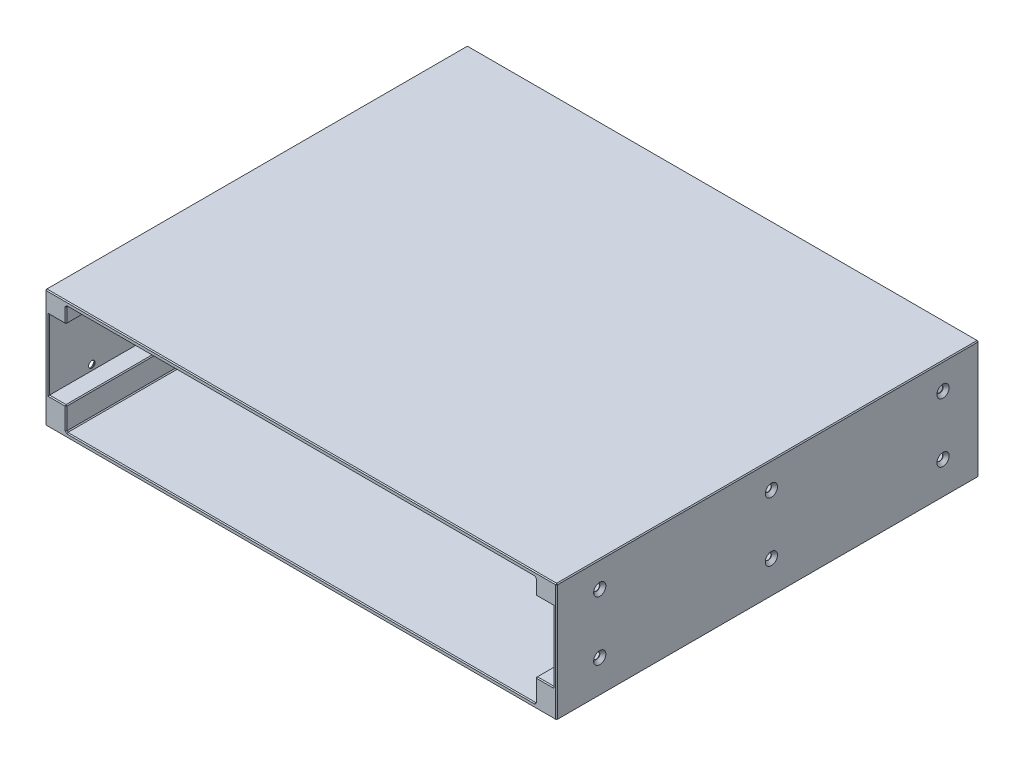
SolidWorks part; units mm, degrees
ref_plane "Front" through (0, 0, 0) normal (0, 0, 1) x (1, 0, 0)
ref_plane "Top" through (0, 0, 0) normal (0, 1, 0) x (1, 0, 0)
ref_plane "Right" through (0, 0, 0) normal (1, 0, 0) x (0, 0, -1)
sketch "Sketch1" plane through (0, 0, 0) normal (0, 0, 1) x (1, 0, 0)
  line L1 (-138, -30) -> (138, -30)
  line L2 (-138, -30) -> (-138, 30)
  line L3 (-138, 30) -> (138, 30)
  line L4 (138, -30) -> (138, 30)
  line L5 (-138, -30) -> (138, 30) construction
  line L6 (-138, 30) -> (138, -30) construction
  point P0 (0, 0)
  dimension "D1" = 276
  dimension "D2" = 60
extrude "Walls" add sketch "Sketch1" along normal blind 230 thin thin type one direction wall 2.5
sketch "Sketch2" plane through (0, 0, 0) normal (0, 0, 1) x (1, 0, 0)
  line L12 (140.5, -32.5) -> (140.5, 32.5)
  line L13 (140.5, 32.5) -> (-140.5, 32.5)
  line L14 (-140.5, 32.5) -> (-140.5, -32.5)
  line L15 (-140.5, -32.5) -> (140.5, -32.5)
  line L16 (140.5, -32.5) -> (140.5, 32.5)
  line L17 (140.5, 32.5) -> (-140.5, 32.5)
  line L18 (-140.5, 32.5) -> (-140.5, -32.5)
  line L19 (-140.5, -32.5) -> (140.5, -32.5)
  dimension "D1" = 0
extrude "Back Plate" add sketch "Sketch2" against normal blind 2
sketch "Sketch7" plane through (138.5, 0, 0) normal (1, 0, 0) x (0, 0, -1)
  line L0 (0, -30) -> (0, 30) construction
  line L1 (0, -17.25) -> (-230, -17.25)
  line L2 (0, -17.25) -> (0, 21.25)
  line L3 (0, 21.25) -> (-230, 21.25)
  line L4 (-230, -17.25) -> (-230, 21.25)
  line L5 (-230, -32.5) -> (-230, 32.5) construction
extrude "Drawer Slide Pocket" cut sketch "Sketch7" against normal up to next
sketch "Sketch8" plane through (138, 0, 0) normal (-1, 0, 0) x (0, 0, 1)
  line L0 (230, 32.5) -> (230, -32.5) construction
  line L1 (0, -30) -> (230, -30)
  line L2 (0, -30) -> (0, -17.25)
  line L3 (0, -17.25) -> (230, -17.25)
  line L4 (230, -30) -> (230, -17.25)
  line L6 (0, 30) -> (230, 30)
  line L7 (0, 30) -> (0, 21.25)
  line L8 (0, 21.25) -> (230, 21.25)
  line L9 (230, 30) -> (230, 21.25)
extrude "Drawer Slide Brackets" add sketch "Sketch8" along normal blind 9
sketch "Sketch9" plane through (140.5, 0, 0) normal (1, 0, 0) x (0, 0, -1)
  point P0 (-206.2857, -14.25)
  point P1 (-206.2857, 18.25)
  point P3 (-112, -14.25)
  point P5 (-112, 18.25)
  point P7 (-17.7143, -14.25)
  point P9 (-17.7143, 18.25)
hole_wizard "CSK for M3 SFHCS1" positions "Sketch9" profile "Sketch10" countersink size "M3" standard "ANSI Metric" end condition up to next
sketch "Sketch10" plane through (140.5, -14.25, 206.2857) normal (0, 1, 0) x (0, 0, -1)
  line L0 (0, 0) -> (0, 2)
  line L1 (0, 2) -> (1.8, 2)
  line L2 (1.7, 1.9) -> (1.7, 1.66)
  line L3 (1.7, 1.66) -> (3.36, 0)
  line L5 (3.36, 0) -> (0, 0)
  line L6 (-1.7, 1.66) -> (-3.36, 0) construction
  line L7 (1.8, 2) -> (1.7, 1.9)
  line L8 (-1.8, 2) -> (-1.7, 1.9) construction
  line L11 (0, -6.35) -> (0, 107.95) construction
  dimension "Thru Hole Dia." = 3.4
  dimension "Thru Hole Depth" = 2
  dimension "Near C'Sink Dia." = 6.72
  dimension "Near C'Sink Angle" = 90
  dimension "Far C'Sink Dia." = 3.6
  dimension "Far C'Sink Angle" = 90
mirror "Drawer Slide Pocket mirror" about plane through (0, 0, 0) normal (1, 0, 0) of "CSK for M3 SFHCS1", "Drawer Slide Pocket", "Drawer Slide Brackets"
sketch "Sketch3" plane through (0, -32.5, 0) normal (0, 1, 0) x (1, 0, 0)
  line L0 (0, 2) -> (0, -114) construction
  line L1 (-114.5192, -23.9808) -> (114.5192, -23.9808) construction
  line L2 (-114.5192, -23.9808) -> (-114.5192, -204.0192) construction
  line L3 (-114.5192, -204.0192) -> (114.5192, -204.0192) construction
  line L4 (114.5192, -23.9808) -> (114.5192, -204.0192) construction
  line L5 (-114.5192, -23.9808) -> (114.5192, -204.0192) construction
  line L6 (-114.5192, -204.0192) -> (114.5192, -23.9808) construction
  line L8 (0, -114) -> (0, -230) construction
  line L10 (-140.5, -23.9808) -> (-114.5192, -23.9808) construction
  line L11 (140.5, 2) -> (-140.5, 2) construction
  line L12 (-114.5192, -23.9808) -> (-114.5192, 2) construction
  line L13 (-57.2596, -23.9808) -> (-57.2596, -15.3205) construction
  line L14 (-114.5192, -32.641) -> (-107.0192, -28.3109)
  line L15 (-107.0192, -28.3109) -> (-107.0192, -19.6506)
  line L16 (-107.0192, -19.6506) -> (-114.5192, -15.3205)
  line L17 (-114.5192, -15.3205) -> (-122.0192, -19.6506)
  line L18 (-122.0192, -19.6506) -> (-122.0192, -28.3109)
  line L19 (-122.0192, -28.3109) -> (-114.5192, -32.641)
  line L20 (-57.2596, -15.3205) -> (-57.2596, -6.6603) construction
  line L21 (0, -114) -> (114.5192, -114) construction
  line L22 (122.0192, -28.3109) -> (114.5192, -32.641)
  line L23 (122.0192, -19.6506) -> (122.0192, -28.3109)
  line L24 (114.5192, -15.3205) -> (122.0192, -19.6506)
  line L25 (107.0192, -19.6506) -> (114.5192, -15.3205)
  line L26 (107.0192, -28.3109) -> (107.0192, -19.6506)
  line L27 (114.5192, -32.641) -> (107.0192, -28.3109)
  line L28 (122.0192, -208.3494) -> (122.0192, -199.6891)
  line L29 (114.5192, -212.6795) -> (122.0192, -208.3494)
  line L30 (107.0192, -208.3494) -> (114.5192, -212.6795)
  line L31 (107.0192, -199.6891) -> (107.0192, -208.3494)
  line L32 (114.5192, -195.359) -> (107.0192, -199.6891)
  line L33 (122.0192, -199.6891) -> (114.5192, -195.359)
  line L34 (-122.0192, -199.6891) -> (-114.5192, -195.359)
  line L35 (-122.0192, -208.3494) -> (-122.0192, -199.6891)
  line L36 (-114.5192, -212.6795) -> (-122.0192, -208.3494)
  line L37 (-107.0192, -208.3494) -> (-114.5192, -212.6795)
  line L38 (-107.0192, -199.6891) -> (-107.0192, -208.3494)
  line L39 (-114.5192, -195.359) -> (-107.0192, -199.6891)
  line L40 (-57.2596, -6.6603) -> (-57.2596, 2) construction
  line L41 (-114.5192, -10.9904) -> (-57.2596, -10.9904) construction
  line L42 (-57.2596, -10.9904) -> (0, -10.9904) construction
  line L43 (-140.5, -230) -> (-140.5, 2) construction
  line L44 (140.5, -230) -> (-140.5, -230) construction
  circle A0 centre (-114.5192, -23.9808) radius 7.5 construction
  point P0 (0, -114)
  point P7 (0, 0)
  point P8 (0, 2)
  point P19 (-140.5, -23.9808)
  point P49 (0, 0)
  point P52 (-57.2596, 2)
  point P54 (0, 0)
  point P55 (0, -230)
  point P58 (0, 0)
  dimension "D1" = 15
extrude "Foot Pocket" cut sketch "Sketch3" along normal blind 1.5 draft 45
sketch "Sketch4" plane through (0, 32.5, 0) normal (0, -1, 0) x (1, 0, 0)
  line L20 (-107.2192, 208.2339) -> (-114.5192, 212.4486)
  line L21 (-114.5192, 212.4486) -> (-121.8192, 208.2339)
  line L22 (-121.8192, 208.2339) -> (-121.8192, 199.8046)
  line L23 (-121.8192, 199.8046) -> (-114.5192, 195.5899)
  line L24 (-114.5192, 195.5899) -> (-107.2192, 199.8046)
  line L25 (-107.2192, 199.8046) -> (-107.2192, 208.2339)
  line L26 (-107.2192, 208.2339) -> (-114.5192, 212.4486)
  line L27 (-114.5192, 212.4486) -> (-121.8192, 208.2339)
  line L28 (-121.8192, 208.2339) -> (-121.8192, 199.8046)
  line L29 (-121.8192, 199.8046) -> (-114.5192, 195.5899)
  line L30 (-114.5192, 195.5899) -> (-107.2192, 199.8046)
  line L31 (-107.2192, 199.8046) -> (-107.2192, 208.2339)
  line L38 (-114.5192, 32.4101) -> (-121.8192, 28.1954)
  line L39 (-121.8192, 28.1954) -> (-121.8192, 19.7661)
  line L40 (-121.8192, 19.7661) -> (-114.5192, 15.5514)
  line L41 (-114.5192, 15.5514) -> (-107.2192, 19.7661)
  line L42 (-107.2192, 19.7661) -> (-107.2192, 28.1954)
  line L43 (-107.2192, 28.1954) -> (-114.5192, 32.4101)
  line L44 (-114.5192, 32.4101) -> (-121.8192, 28.1954)
  line L45 (-121.8192, 28.1954) -> (-121.8192, 19.7661)
  line L46 (-121.8192, 19.7661) -> (-114.5192, 15.5514)
  line L47 (-114.5192, 15.5514) -> (-107.2192, 19.7661)
  line L48 (-107.2192, 19.7661) -> (-107.2192, 28.1954)
  line L49 (-107.2192, 28.1954) -> (-114.5192, 32.4101)
  line L56 (114.5192, 212.4486) -> (107.2192, 208.2339)
  line L57 (107.2192, 208.2339) -> (107.2192, 199.8046)
  line L58 (107.2192, 199.8046) -> (114.5192, 195.5899)
  line L59 (114.5192, 195.5899) -> (121.8192, 199.8046)
  line L60 (121.8192, 199.8046) -> (121.8192, 208.2339)
  line L61 (121.8192, 208.2339) -> (114.5192, 212.4486)
  line L62 (114.5192, 212.4486) -> (107.2192, 208.2339)
  line L63 (107.2192, 208.2339) -> (107.2192, 199.8046)
  line L64 (107.2192, 199.8046) -> (114.5192, 195.5899)
  line L65 (114.5192, 195.5899) -> (121.8192, 199.8046)
  line L66 (121.8192, 199.8046) -> (121.8192, 208.2339)
  line L67 (121.8192, 208.2339) -> (114.5192, 212.4486)
  line L74 (121.8192, 19.7661) -> (121.8192, 28.1954)
  line L75 (114.5192, 15.5514) -> (121.8192, 19.7661)
  line L76 (107.2192, 19.7661) -> (114.5192, 15.5514)
  line L77 (107.2192, 28.1954) -> (107.2192, 19.7661)
  line L78 (114.5192, 32.4101) -> (107.2192, 28.1954)
  line L79 (121.8192, 28.1954) -> (114.5192, 32.4101)
  line L80 (121.8192, 19.7661) -> (121.8192, 28.1954)
  line L81 (114.5192, 15.5514) -> (121.8192, 19.7661)
  line L82 (107.2192, 19.7661) -> (114.5192, 15.5514)
  line L83 (107.2192, 28.1954) -> (107.2192, 19.7661)
  line L84 (114.5192, 32.4101) -> (107.2192, 28.1954)
  line L85 (121.8192, 28.1954) -> (114.5192, 32.4101)
  dimension "D1" = 0.2
  dimension "D2" = 0.2
  dimension "D3" = 0.2
  dimension "D4" = 0.2
extrude "Feet" [suppressed] add sketch "Sketch4" against normal blind 1.3 draft 45
chamfer "Deburs 1" distance 0.5 angle 45 34 edges at (-138.5, 2, 230) (-133.75, -17.25, 230) (-129, -17.25, 115) (-129, -23.625, 230) (0, -30, 230) (0, 30, 230) (-133.75, 21.25, 230) (-129, 21.25, 115) (-129, 25.625, 230) (-129, 30, 115) (0, 30, 0) (129, 30, 115) (129, 25.625, 230) (129, 21.25, 115) (133.75, 21.25, 230) (138.5, 2, 230) (133.75, -17.25, 230) (129, -17.25, 115) (129, -23.625, 230) (-129, -30, 115) (0, -30, 0) (129, -30, 115) (140.5, 0, 230) (0, -32.5, 230) (-140.5, 0, 230) (0, 32.5, 230) (-140.5, 0, -2) (-140.5, 32.5, 114) (0, 32.5, -2) (140.5, 32.5, 114) (140.5, 0, -2) (140.5, -32.5, 114) (0, -32.5, -2) (-140.5, -32.5, 114)
chamfer "Deburs 2" distance 0.5 angle 45 4 edges at (129, -23.625, 0) (129, 25.625, 0) (-129, 25.625, 0) (-129, -23.625, 0)
